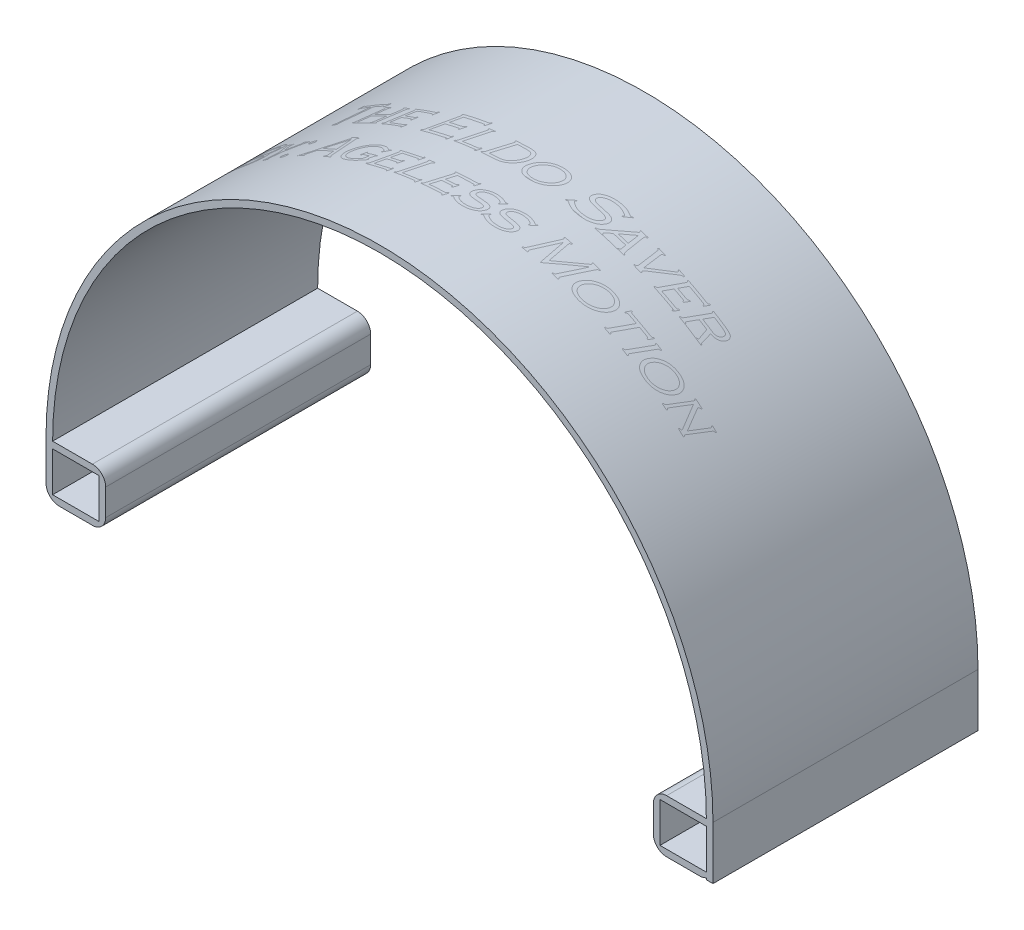
SolidWorks part; units mm, degrees
material "Nylon 6/10"
ref_plane "Front Plane" through (0, 0, 0) normal (0, 0, 1) x (1, 0, 0)
ref_plane "Top Plane" through (0, 0, 0) normal (0, 1, 0) x (1, 0, 0)
ref_plane "Right Plane" through (0, 0, 0) normal (1, 0, 0) x (0, 0, -1)
sketch "Sketch1" plane through (0, 0, 0) normal (0, 0, 1) x (1, 0, 0)
  line L0 (-74, 0) -> (74, 0) construction
  line L1 (-74, 0) -> (-75.5, 0)
  line L2 (74, 0) -> (75.5, 0)
  arc A0 (74, 0) -> (-74, 0) centre (0, 0) ccw
  arc A1 (75.5, 0) -> (-75.5, 0) centre (0, 0) ccw
  dimension "D1" = 74
  dimension "D2" = 1.5
extrude "Boss-Extrude2" add sketch "Sketch1" along normal mid plane 60
ref_plane "Plane1" through (0, 150, 0) normal (0, 1, 0) x (1, 0, 0)
sketch "Sketch3" plane through (0, 150, 0) normal (0, 1, 0) x (1, 0, 0)
  line L0 (-115.5974, 0) -> (115.5974, 0)
  text T0 "<i>The Eldo Saver</i>\r\n<i>By: Ageless Motion</i>" font "Copperplate Gothic Light" height in points 36
  point P4 (0, 0)
wrap "Wrap1" sketch "Sketch3" wrap type scribe source sketch "Sketch3" face at (0, 37.75, 0)
sketch "Sketch4" plane through (0, 0, 0) normal (0, -1, 0) x (1, 0, 0)
  line L1 (-75.5, 30) -> (-74, 30)
  line L2 (-75.5, 30) -> (-75.5, -30)
  line L3 (-75.5, -30) -> (-74, -30)
  line L4 (-74, 30) -> (-74, -30)
  line L5 (74, 30) -> (75.5, 30)
  line L6 (74, 30) -> (74, -30)
  line L7 (74, -30) -> (75.5, -30)
  line L8 (75.5, 30) -> (75.5, -30)
extrude "Boss-Extrude3" add sketch "Sketch4" along normal blind 12
sketch "Sketch5" plane through (74, 0, 0) normal (-1, 0, 0) x (0, 0, 1)
  line L0 (30, -12) -> (30, 0) construction
  line L1 (-30, -12) -> (30, -12)
  line L2 (-30, -12) -> (-30, -10.5)
  line L3 (-30, -10.5) -> (30, -10.5)
  line L4 (30, -12) -> (30, -10.5)
  dimension "D1" = 1.5
extrude "Boss-Extrude4" add sketch "Sketch5" along normal blind 12
sketch "Sketch6" plane through (0, -10.5, 0) normal (0, 1, 0) x (1, 0, 0)
  line L0 (-75.5, -30) -> (75.5, -30) construction
  line L1 (62, 30) -> (63.5, 30)
  line L2 (62, 30) -> (62, -30)
  line L3 (62, -30) -> (63.5, -30)
  line L4 (63.5, 30) -> (63.5, -30)
  dimension "D1" = 1.5
extrude "Boss-Extrude5" add sketch "Sketch6" along normal blind 10.5
sketch "Sketch9" plane through (63.5, 0, 0) normal (1, 0, 0) x (0, 0, -1)
  line L0 (30, -12) -> (30, 0) construction
  line L1 (-30, 0) -> (30, 0)
  line L2 (-30, 0) -> (-30, -1.5)
  line L3 (-30, -1.5) -> (30, -1.5)
  line L4 (30, 0) -> (30, -1.5)
  dimension "D1" = 1.5
extrude "Boss-Extrude6" add sketch "Sketch9" along normal up to next
fillet "Fillet1" radius 3 3 edges at (62, -12, 0) (75.5, -12, 0) (62, 0, 0)
mirror "Mirror11" about plane through (0, 0, 0) normal (1, 0, 0) of "Boss-Extrude3", "Boss-Extrude4", "Boss-Extrude5", "Boss-Extrude6"
fillet "Fillet3" radius 3 3 edges at (-75.5, -12, 0) (-62, -12, 0) (-62, 0, 0)
